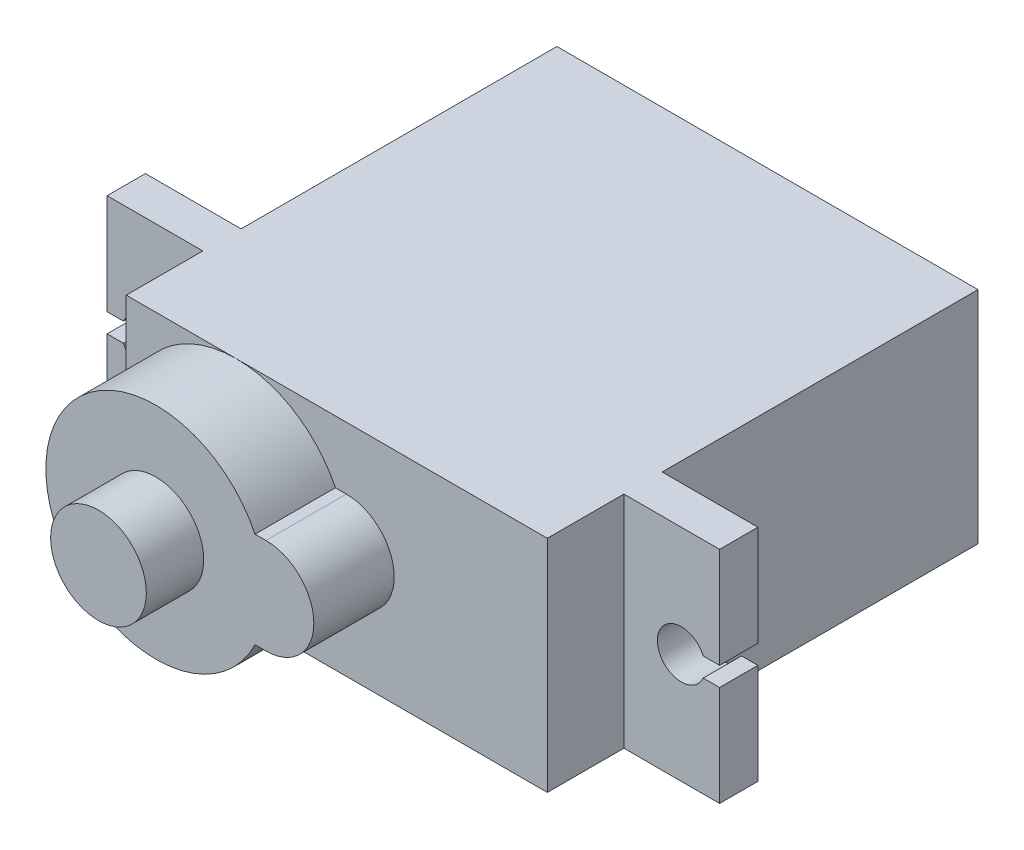
SolidWorks part; units mm, degrees
ref_plane "Plan de face" through (0, 0, 0) normal (0, 0, 1) x (1, 0, 0)
ref_plane "Plan de dessus" through (0, 0, 0) normal (0, 1, 0) x (1, 0, 0)
ref_plane "Plan de droite" through (0, 0, 0) normal (1, 0, 0) x (0, 0, -1)
sketch "Esquisse1" plane through (0, 0, 0) normal (0, 0, 1) x (1, 0, 0)
  line L1 (0, 0) -> (-22, 0)
  line L2 (0, 0) -> (0, 11.5)
  line L3 (0, 11.5) -> (-22, 11.5)
  line L4 (-22, 0) -> (-22, 11.5)
  dimension "D1" = 22
  dimension "D2" = 11.5
extrude "Boss.-Extru.1" add sketch "Esquisse1" along normal blind 22.5
ref_plane "Plan1" through (0, 0, 18.5) normal (0, 0, 1) x (1, 0, 0)
sketch "Esquisse2" plane through (0, 0, 18.5) normal (0, 0, 1) x (1, 0, 0)
  line L0 (0, 11.5) -> (-22, 11.5) construction
  line L1 (-27, 11.5) -> (5, 11.5)
  line L2 (-27, 11.5) -> (-27, 0)
  line L3 (-27, 0) -> (5, 0)
  line L4 (5, 11.5) -> (5, 0)
  line L5 (-22, 0) -> (0, 0) construction
  point P4 (-11, 11.5)
  point P5 (-11, 11.5)
  dimension "D1" = 32
extrude "Boss.-Extru.2" add sketch "Esquisse2" against normal blind 2
sketch "Esquisse3" plane through (0, 0, 18.5) normal (0, 0, 1) x (1, 0, 0)
  line L0 (-27, 5.75) -> (5, 5.75) construction
  line L1 (-27, 11.5) -> (-27, 0) construction
  line L2 (5, 0) -> (5, 11.5) construction
  line L3 (-11, 5.75) -> (-11, 17.6002) construction
  line L4 (4.1456, 6.25) -> (5, 6.25)
  line L5 (5, 6.25) -> (5, 5.25)
  line L6 (4.1456, 5.25) -> (5, 5.25)
  line L7 (-26.1456, 5.25) -> (-27, 5.25)
  line L8 (-27, 6.25) -> (-27, 5.25)
  line L9 (-26.1456, 6.25) -> (-27, 6.25)
  arc A0 (4.1456, 6.25) -> (4.1456, 5.25) centre (3, 5.75) ccw
  circle A1 centre (3, 5.75) radius 1.25 construction
  circle A2 centre (-25, 5.75) radius 1.25 construction
  arc A3 (-26.1456, 6.25) -> (-26.1456, 5.25) centre (-25, 5.75) cw
  dimension "D1" = 2.5
  dimension "D2" = 1
  dimension "D3" = 28
extrude "Enlèv. mat.-Extru.1" cut sketch "Esquisse3" against normal through all
sketch "Esquisse4" plane through (0, 0, 22.5) normal (0, 0, 1) x (1, 0, 0)
  line L0 (0, 11.5) -> (-22, 11.5) construction
  line L1 (-22, 11.5) -> (-22, 0) construction
  line L2 (-22, 0) -> (0, 0) construction
  line L3 (-10.5, 8.25) -> (-11.0719, 8.25)
  line L4 (-10.5, 3.25) -> (-11.0719, 3.25)
  line L5 (-25, 5.75) -> (-10.5, 5.75) construction
  circle A0 centre (-16.25, 5.75) radius 5.75 construction
  circle A1 centre (-10.5, 5.75) radius 2.5 construction
  arc A2 (-10.5, 8.25) -> (-10.5, 3.25) centre (-10.5, 5.75) cw
  arc A3 (-11.0719, 8.25) -> (-11.0719, 3.25) centre (-16.25, 5.75) ccw
  point P16 (-13, 5.75)
  point P17 (-22, 5.75)
  point P19 (-8, 5.75)
  dimension "D1" = 5
  dimension "D2" = 14
extrude "Boss.-Extru.3" add sketch "Esquisse4" along normal blind 4.2
sketch "Esquisse5" plane through (0, 0, 26.7) normal (0, 0, 1) x (1, 0, 0)
  circle A0 centre (-16.25, 5.75) radius 2.5
  dimension "D1" = 5
extrude "Boss.-Extru.4" add sketch "Esquisse5" along normal blind 3
sketch "Sketch1" plane through (0, 0, 0) normal (0, 0, 1) x (1, 0, 0)
  line L0 (-26.1456, 5.25) -> (-27, 5.25) construction
  line L1 (-27, 5.25) -> (-27, 0) construction
  line L2 (-27, 0) -> (-22, 0) construction
  line L3 (-22, 0) -> (-22, 11.5) construction
  line L4 (-22, 11.5) -> (-27, 11.5) construction
  line L5 (-27, 11.5) -> (-27, 6.25) construction
  line L6 (-27, 6.25) -> (-26.1456, 6.25) construction
  line L7 (-16.25, 11.5) -> (-22, 11.5) construction
  line L8 (-22, 11.5) -> (-22, 5.75) construction
  line L9 (-10.5, 8.25) -> (-11.0719, 8.25) construction
  line L10 (-11.0719, 3.25) -> (-10.5, 3.25) construction
  line L11 (-16.25, 0) -> (0, 0) construction
  line L12 (0, 0) -> (0, 11.5) construction
  line L13 (0, 11.5) -> (-16.25, 11.5) construction
  line L14 (-11.0719, 8.25) -> (-10.5, 8.25) construction
  line L15 (-10.5, 3.25) -> (-11.0719, 3.25) construction
  line L16 (4.1456, 6.25) -> (5, 6.25) construction
  line L17 (5, 6.25) -> (5, 11.5) construction
  line L18 (5, 11.5) -> (0, 11.5) construction
  line L19 (0, 11.5) -> (0, 0) construction
  line L20 (0, 0) -> (5, 0) construction
  line L21 (5, 0) -> (5, 5.25) construction
  line L22 (5, 5.25) -> (4.1456, 5.25) construction
  line L23 (-26.1456, 5.25) -> (-27, 5.25)
  line L24 (-27, 5.25) -> (-27, 0)
  line L25 (-27, 0) -> (-22, 0)
  line L26 (-22, 0) -> (-22, 11.5)
  line L27 (-22, 11.5) -> (-27, 11.5)
  line L28 (-27, 11.5) -> (-27, 6.25)
  line L29 (-27, 6.25) -> (-26.1456, 6.25)
  line L30 (-16.25, 11.5) -> (-22, 11.5)
  line L31 (-22, 11.5) -> (-22, 5.75)
  line L32 (-10.5, 8.25) -> (-11.0719, 8.25)
  line L33 (-11.0719, 3.25) -> (-10.5, 3.25)
  line L34 (-16.25, 0) -> (0, 0)
  line L35 (0, 0) -> (0, 11.5)
  line L36 (0, 11.5) -> (-16.25, 11.5)
  line L37 (-11.0719, 8.25) -> (-10.5, 8.25)
  line L38 (-10.5, 3.25) -> (-11.0719, 3.25)
  line L39 (4.1456, 6.25) -> (5, 6.25)
  line L40 (5, 6.25) -> (5, 11.5)
  line L41 (5, 11.5) -> (0, 11.5)
  line L42 (0, 11.5) -> (0, 0)
  line L43 (0, 0) -> (5, 0)
  line L44 (5, 0) -> (5, 5.25)
  line L45 (5, 5.25) -> (4.1456, 5.25)
  arc A0 (-26.1456, 5.25) -> (-26.1456, 6.25) centre (-25, 5.75) ccw construction
  arc A1 (-16.25, 11.5) -> (-22, 5.75) centre (-16.25, 5.75) ccw construction
  arc A2 (-10.5, 3.25) -> (-10.5, 8.25) centre (-10.5, 5.75) ccw construction
  arc A3 (-11.0719, 8.25) -> (-11.0719, 3.25) centre (-16.25, 5.75) ccw construction
  arc A4 (-16.25, 0) -> (-11.0719, 3.25) centre (-16.25, 5.75) ccw construction
  arc A5 (-11.0719, 8.25) -> (-16.25, 11.5) centre (-16.25, 5.75) ccw construction
  arc A6 (-10.5, 3.25) -> (-10.5, 8.25) centre (-10.5, 5.75) ccw construction
  arc A7 (4.1456, 6.25) -> (4.1456, 5.25) centre (3, 5.75) ccw construction
  arc A8 (-26.1456, 5.25) -> (-26.1456, 6.25) centre (-25, 5.75) ccw
  arc A9 (-16.25, 11.5) -> (-22, 5.75) centre (-16.25, 5.75) ccw
  arc A10 (-10.5, 3.25) -> (-10.5, 8.25) centre (-10.5, 5.75) ccw
  arc A11 (-11.0719, 8.25) -> (-11.0719, 3.25) centre (-16.25, 5.75) ccw
  arc A12 (-16.25, 0) -> (-11.0719, 3.25) centre (-16.25, 5.75) ccw
  arc A13 (-11.0719, 8.25) -> (-16.25, 11.5) centre (-16.25, 5.75) ccw
  arc A14 (-10.5, 3.25) -> (-10.5, 8.25) centre (-10.5, 5.75) ccw
  arc A15 (4.1456, 6.25) -> (4.1456, 5.25) centre (3, 5.75) ccw
